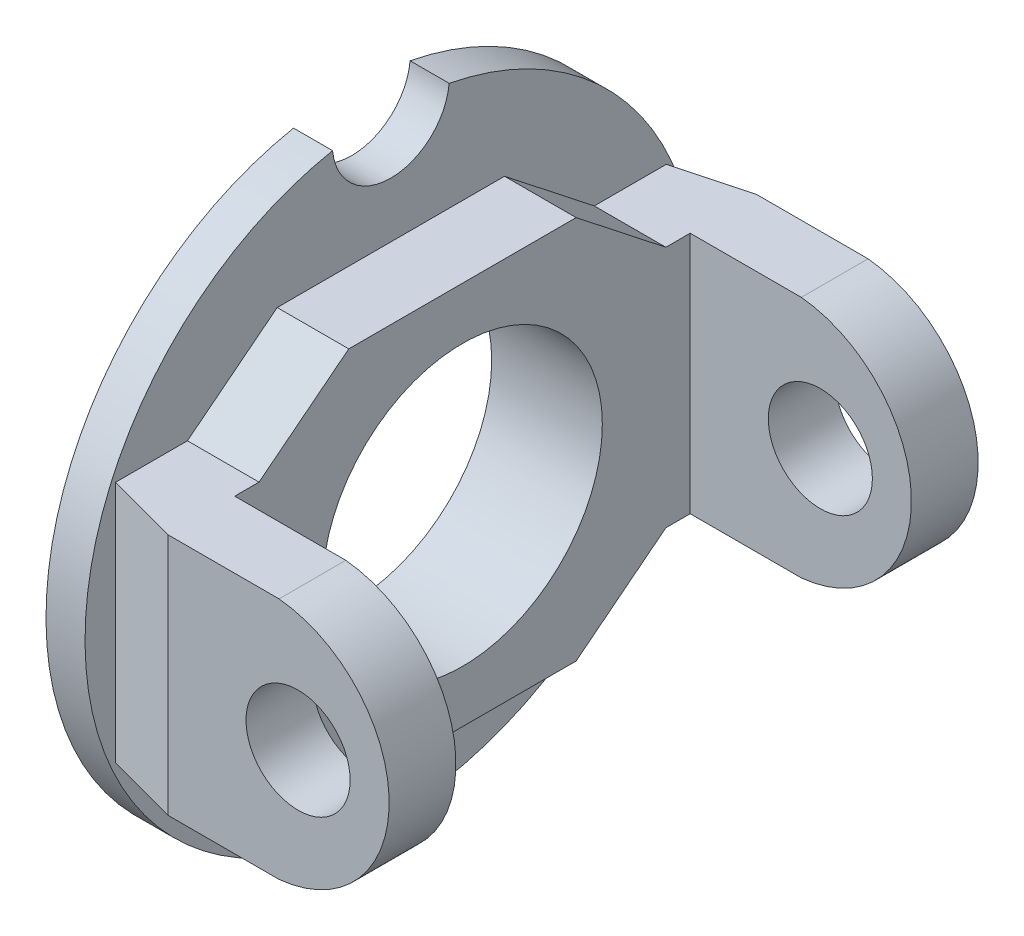
SolidWorks part; units mm, degrees
material "1060 Alloy"
ref_plane "Front Plane" through (0, 0, 0) normal (0, 0, 1) x (1, 0, 0)
ref_plane "Top Plane" through (0, 0, 0) normal (0, 1, 0) x (1, 0, 0)
ref_plane "Right Plane" through (0, 0, 0) normal (1, 0, 0) x (0, 0, -1)
sketch "Sketch1" plane through (0, 0, 0) normal (1, 0, 0) x (0, 0, -1)
  line L0 (0, 0) -> (0, 19) construction
  arc A0 (-4.4793, 23.0691) -> (4.4793, 23.0691) centre (0, 0) ccw
  circle A1 centre (0, 0) radius 10.75
  arc A2 (-4.4793, 23.0691) -> (4.4793, 23.0691) centre (0, 23.5) ccw
  dimension "D1" = 47
  dimension "D2" = 21.5
  dimension "D4" = 9
  dimension "D3" = 23.5
extrude "Boss-Extrude1" add sketch "Sketch1" along normal blind 3
sketch "Sketch2" plane through (3, 0, 0) normal (1, 0, 0) x (0, 0, -1)
  line L0 (-15.63, 9.335) -> (-8.735, 14.7546)
  line L1 (-22.63, 9.335) -> (-15.63, 9.335)
  line L2 (-22.63, 9.335) -> (-22.63, -9.335)
  line L3 (-22.63, -9.335) -> (-15.63, -9.335)
  line L4 (-15.63, 9.335) -> (-15.63, -9.335)
  line L5 (15.63, 9.335) -> (22.63, 9.335)
  line L6 (15.63, 9.335) -> (15.63, -9.335)
  line L7 (15.63, -9.335) -> (22.63, -9.335)
  line L8 (22.63, 9.335) -> (22.63, -9.335)
  line L9 (-8.735, 14.7546) -> (8.735, 14.7546)
  line L10 (8.735, 14.7546) -> (15.63, 9.335)
  line L11 (-15.63, -9.335) -> (-8.735, -14.7546)
  line L12 (-8.735, -14.7546) -> (8.735, -14.7546)
  line L13 (8.735, -14.7546) -> (15.63, -9.335)
  line L14 (0, 14.7546) -> (0, -14.7546) construction
  line L15 (-15.63, 0) -> (15.63, 0) construction
  arc M18 (-4.4793, 23.0691) -> (4.4793, 23.0691) centre (0, 0) ccw
  circle M19 centre (0, 0) radius 10.75
  dimension "D1" = 18.67
  dimension "D2" = 7
  dimension "D3" = 15.63
  dimension "D4" = 7
  dimension "D5" = 17.47
  dimension "D6" = 8.77
  dimension "D7" = 8.77
extrude "Boss-Extrude2" add sketch "Sketch2" along normal blind 5.5 contours L1 L2 M18 | L4 L1 L2 L3 M18 | L2 L3 M18 | L12 L13 L6 L10 L9 L0 L4 L11 M19 | L8 L5 L6 L7 M18 | L8 L7 M18 | L8 L5 M18 region at (3, 0, 19.0568) region at (3, 11.7068, 11.9168) region at (3, 8.3731, 22.2876) region at (3, -8.3731, 22.2876) region at (3, 0, -19.0568) region at (3, -8.3731, -22.2876) region at (3, 8.3731, -22.2876)
draft "Draft1" type of draft neutral plane draft angle 15 faces to draft 2 face at (4.8333, 0, -22.63) face at (4.8333, 0, 22.63) neutral plane through (8.5, 0, 0) neutral plane normal (1, 0, 0) reverse direction yes parameters "D1"=15
sketch "Sketch3" plane through (8.5, 0, 0) normal (1, 0, 0) x (0, 0, -1)
  line L0 (-22.63, -9.335) -> (-15.63, -9.335) construction
  line L1 (-22.63, 9.335) -> (-17.5, 9.335)
  line L2 (-22.63, 9.335) -> (-22.63, -9.335)
  line L3 (-22.63, -9.335) -> (-17.5, -9.335)
  line L4 (-17.5, 9.335) -> (-17.5, -9.335)
  line L5 (15.63, -9.335) -> (22.63, -9.335) construction
  line L6 (22.63, 9.335) -> (17.5, 9.335)
  line L7 (22.63, 9.335) -> (22.63, -9.335)
  line L8 (22.63, -9.335) -> (17.5, -9.335)
  line L9 (17.5, 9.335) -> (17.5, -9.335)
  dimension "D1" = 35
  dimension "D2" = 17.5
extrude "Boss-Extrude3" add sketch "Sketch3" along normal blind 17
sketch "Sketch4" plane through (0, 0, 22.63) normal (0, 0, 1) x (1, 0, 0)
  line L1 (17.0377, 12.875) -> (29.4777, 12.875)
  line L3 (17.0377, -13.095) -> (29.4777, -13.095)
  line L4 (29.4777, 12.875) -> (29.4777, -13.095)
  line L8 (17.0377, 12.875) -> (17.0377, 9.335)
  line L9 (25.5, 9.335) -> (8.5, 9.335) construction
  line L10 (25.5, -9.335) -> (8.5, -9.335) construction
  line L11 (17.0377, -9.335) -> (17.0377, -13.095)
  line L12 (25.5, 9.335) -> (25.5, -9.335) construction
  arc A0 (17.0377, 9.335) -> (17.0377, -9.335) centre (16.12, 0) cw
  dimension "D4" = 9.38
  dimension "D1" = 25.97
  dimension "D2" = 3.54
  dimension "D3" = 12.44
extrude "Cut-Extrude1" cut sketch "Sketch4" against normal up to surface (45.26 mm away) up to face at (17, 0, -22.63)
sketch "Sketch5" plane through (0, 0, 22.63) normal (0, 0, 1) x (1, 0, 0)
  line L0 (25.5, 0) -> (18.5, 0) construction
  circle A0 centre (18.5, 0) radius 4
  arc A1 (17.0377, -9.335) -> (17.0377, 9.335) centre (16.12, 0) ccw construction
  dimension "D1" = 8
  dimension "D2" = 7
extrude "Cut-Extrude2" cut sketch "Sketch5" against normal up to surface (45.26 mm away) up to face at (14.8844, 0, -22.63)
